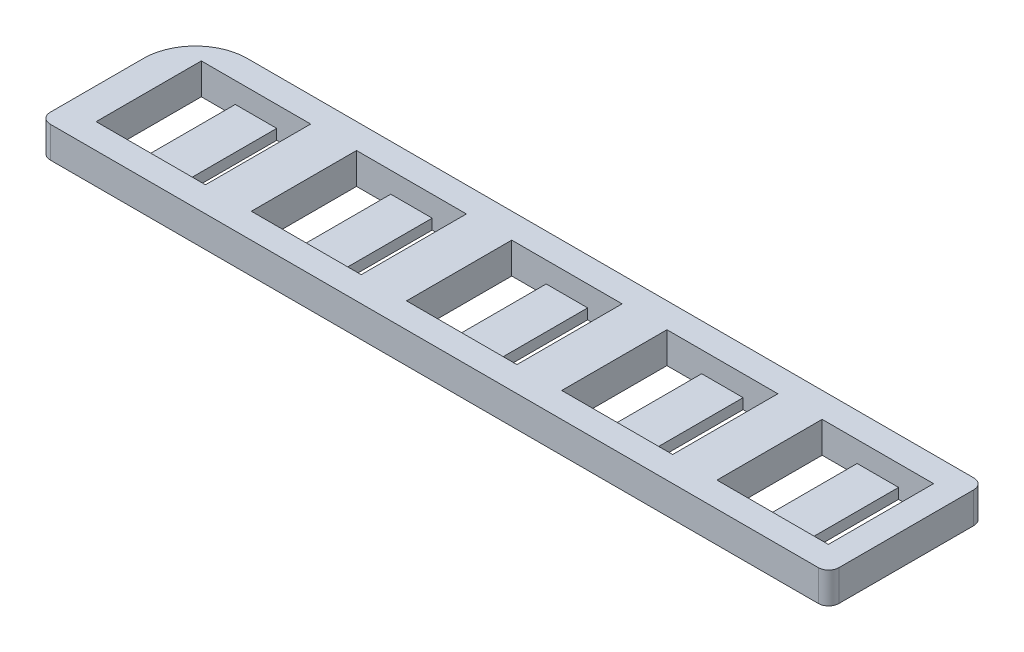
SolidWorks part; units mm, degrees
ref_plane "Front Plane" through (0, 0, 0) normal (0, 0, 1) x (1, 0, 0)
ref_plane "Top Plane" through (0, 0, 0) normal (0, 1, 0) x (1, 0, 0)
ref_plane "Right Plane" through (0, 0, 0) normal (1, 0, 0) x (0, 0, -1)
sketch "Sketch1" plane through (0, 0, 0) normal (0, 1, 0) x (1, 0, 0)
  line L0 (-139.2244, 0) -> (96.0116, 0) construction
  line L1 (0, 92.8454) -> (0, -61.6194) construction
  line L2 (-31.775, 5.075) -> (-31.775, -5.075)
  line L3 (-38.05, -7.5) -> (38.05, -7.5)
  line L4 (-38.05, -7.5) -> (-38.05, 7.5)
  line L5 (-38.05, 7.5) -> (38.05, 7.5)
  line L6 (38.05, -7.5) -> (38.05, 7.5)
  line L7 (-38.05, -7.5) -> (38.05, 7.5) construction
  line L8 (-38.05, 7.5) -> (38.05, -7.5) construction
  line L9 (-35.05, -5.075) -> (-24.5, -5.075)
  line L10 (-35.05, -5.075) -> (-35.05, 5.075)
  line L11 (-35.05, 5.075) -> (-24.5, 5.075)
  line L12 (-24.5, -5.075) -> (-24.5, 5.075)
  line L13 (-35.05, -5.075) -> (-24.5, 5.075) construction
  line L14 (-35.05, 5.075) -> (-24.5, -5.075) construction
  line L15 (-27.775, 5.075) -> (-27.775, -5.075)
  line L16 (-29.775, 5.075) -> (-29.775, -5.075) construction
  line L17 (-16.775, 5.075) -> (-16.775, -5.075)
  line L18 (-20.075, -5.075) -> (-9.475, -5.075)
  line L19 (-20.075, -5.075) -> (-20.075, 5.075)
  line L20 (-20.075, 5.075) -> (-9.475, 5.075)
  line L21 (-9.475, -5.075) -> (-9.475, 5.075)
  line L22 (-20.075, -5.075) -> (-9.475, 5.075) construction
  line L23 (-20.075, 5.075) -> (-9.475, -5.075) construction
  line L24 (-12.775, 5.075) -> (-12.775, -5.075)
  line L25 (-14.775, 5.075) -> (-14.775, -5.075) construction
  line L26 (-1.775, 5.075) -> (-1.775, -5.075)
  line L27 (-5.1, -5.075) -> (5.55, -5.075)
  line L28 (-5.1, -5.075) -> (-5.1, 5.075)
  line L29 (-5.1, 5.075) -> (5.55, 5.075)
  line L30 (5.55, -5.075) -> (5.55, 5.075)
  line L31 (-5.1, -5.075) -> (5.55, 5.075) construction
  line L32 (-5.1, 5.075) -> (5.55, -5.075) construction
  line L33 (2.225, 5.075) -> (2.225, -5.075)
  line L34 (0.225, 5.075) -> (0.225, -5.075) construction
  line L35 (13.225, 5.075) -> (13.225, -5.075)
  line L36 (9.875, -5.075) -> (20.575, -5.075)
  line L37 (9.875, -5.075) -> (9.875, 5.075)
  line L38 (9.875, 5.075) -> (20.575, 5.075)
  line L39 (20.575, -5.075) -> (20.575, 5.075)
  line L40 (9.875, -5.075) -> (20.575, 5.075) construction
  line L41 (9.875, 5.075) -> (20.575, -5.075) construction
  line L42 (17.225, 5.075) -> (17.225, -5.075)
  line L43 (15.225, 5.075) -> (15.225, -5.075) construction
  line L44 (28.225, 5.075) -> (28.225, -5.075)
  line L45 (24.85, -5.075) -> (35.6, -5.075)
  line L46 (24.85, -5.075) -> (24.85, 5.075)
  line L47 (24.85, 5.075) -> (35.6, 5.075)
  line L48 (35.6, -5.075) -> (35.6, 5.075)
  line L49 (24.85, -5.075) -> (35.6, 5.075) construction
  line L50 (24.85, 5.075) -> (35.6, -5.075) construction
  line L51 (32.225, 5.075) -> (32.225, -5.075)
  line L52 (30.225, 5.075) -> (30.225, -5.075) construction
  point P5 (0, 0)
  point P11 (-29.775, 0)
  point P22 (-14.775, 0)
  point P34 (0.225, 0)
  point P46 (15.225, 0)
  point P58 (30.225, 0)
  dimension "D3" = 10.55
  dimension "D4" = 3
  dimension "D5" = 2
  dimension "D6" = 2
  dimension "D7" = 10.6
  dimension "D8" = 15
  dimension "D9" = 2
  dimension "D10" = 10.65
  dimension "D11" = 15
  dimension "D12" = 2
  dimension "D13" = 10.7
  dimension "D14" = 15
  dimension "D15" = 2
  dimension "D16" = 10.75
  dimension "D17" = 15
  dimension "D18" = 10.15
  dimension "D1" = 76.1
  dimension "D2" = 15
extrude "Boss-Extrude1" add sketch "Sketch1" along normal blind 3 contours L3 L6 L5 L4 L48 L45 L46 L47 L39 L36 L37 L38 L30 L27 L28 L29 L21 L18 L19 L20 L12 L9 L10 L11 region at (-37.2744, 0, 0)
extrude "Boss-Extrude2" add sketch "Sketch1<3>" along normal blind 1 contours L15 L11 L2 L9 | L24 L20 L17 L18 | L33 L29 L26 L27 | L42 L38 L35 L36 | L51 L47 L44 L45 region at (-29.775, 0, 0) region at (-14.775, 0, 0) region at (0.225, 0, 0) region at (15.225, 0, 0) region at (30.225, 0, 0)
sketch "Sketch1<3>" plane through (0, 0, 0) normal (0, 1, 0) x (1, 0, 0) same geometry as "Sketch1"
fillet "Fillet1" radius 5 1 edges at (-38.05, 1.5, -7.5)
fillet "Fillet2" radius 1 3 edges at (38.05, 1.5, -7.5) (38.05, 1.5, 7.5) (-38.05, 1.5, 7.5)
